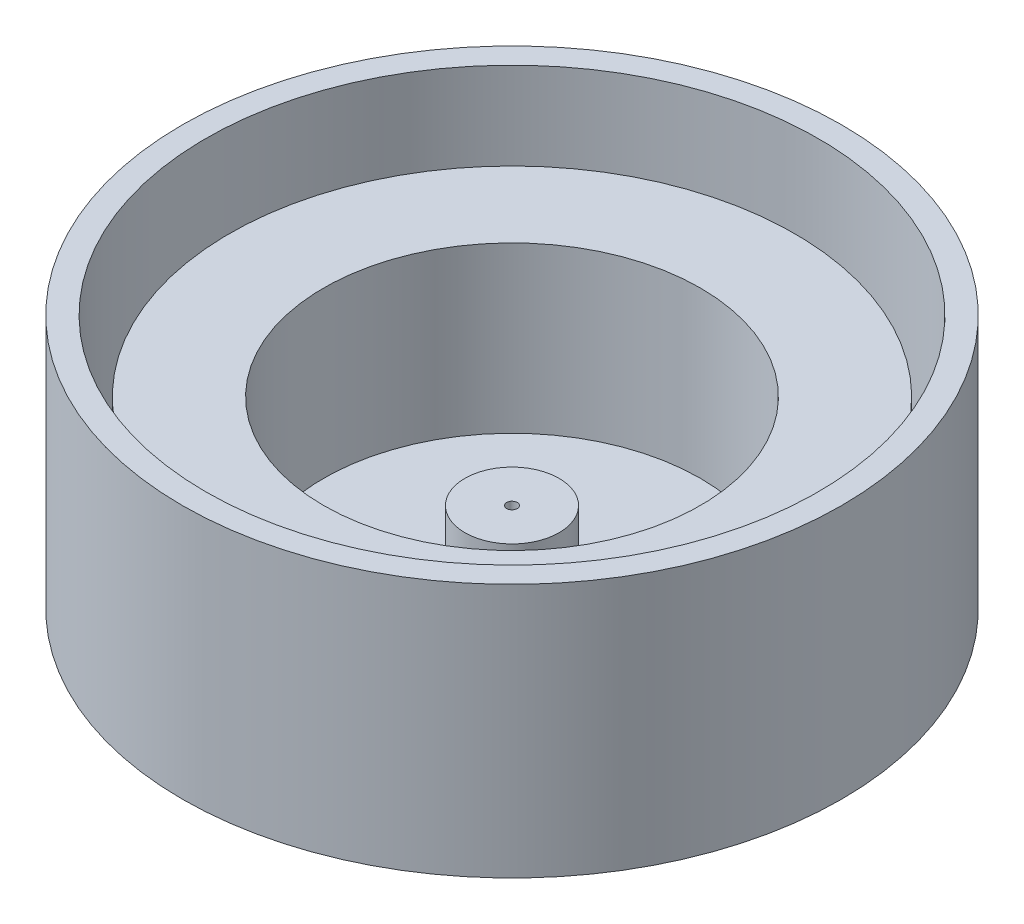
SolidWorks part; units mm, degrees
ref_plane "Front Plane" through (0, 0, 0) normal (0, 0, 1) x (1, 0, 0)
ref_plane "Top Plane" through (0, 0, 0) normal (0, 1, 0) x (1, 0, 0)
ref_plane "Right Plane" through (0, 0, 0) normal (1, 0, 0) x (0, 0, -1)
sketch "Sketch1" plane through (0, 0, 0) normal (0, 1, 0) x (1, 0, 0)
  circle A0 centre (0, 0) radius 70
  circle A1 centre (0, 0) radius 65
  circle A2 centre (0, 0) radius 1.125
  circle A3 centre (0, 0) radius 10
  circle A4 centre (0, 0) radius 40
  circle A5 centre (0, 0) radius 60
  dimension "D1" = 140
  dimension "D3" = 2.25
  dimension "D5" = 80
  dimension "D6" = 20
  dimension "D2" = 5
  dimension "D4" = 20
extrude "Boss-Extrude2" add sketch "Sketch1" against normal blind 4 contours A1 A5 | A4 A3 | A0 A1 | A5 A4 | A3 A2 | A2 region at (-68.0201, 0, 0) region at (-63.1615, 0, 0) region at (0, 0, 0) region at (-9.7172, 0, 0) region at (-38.8686, 0, 0) region at (-58.3029, 0, 0)
extrude "Boss-Extrude3" add sketch "Sketch1<6>" along normal blind 15 contours A3 A2 region at (-9.7172, 0, 0)
sketch "Sketch1<6>" plane through (0, 0, 0) normal (0, 1, 0) x (1, 0, 0) same geometry as "Sketch1"
extrude "Boss-Extrude4" add sketch "Sketch1<7>" along normal blind 50 contours A0 A1 region at (-68.0201, 0, 0)
sketch "Sketch1<7>" plane through (0, 0, 0) normal (0, 1, 0) x (1, 0, 0) same geometry as "Sketch1"
extrude "Boss-Extrude5" add sketch "Sketch1<8>" along normal blind 35 contours A5 A4 region at (-58.3029, 0, 0)
sketch "Sketch1<8>" plane through (0, 0, 0) normal (0, 1, 0) x (1, 0, 0) same geometry as "Sketch1"
equation "\"Outer_Diamter\"=140"
equation "\"D1@Sketch1\"=\"Outer_Diamter\""
equation "\"steelShaftDIa\"=2"
equation "\"D3@Sketch1\"=\"steelShaftDIa\" + 0.25mm"
equation "\"trackID\"=80"
equation "\"D5@Sketch1\"=\"trackID\""
equation "\"trackWidth\"=20"
equation "\"D4@Sketch1\"=\"trackWidth\""
equation "\"guidingShaft\"=20"
equation "\"D6@Sketch1\"=\"guidingShaft\""
